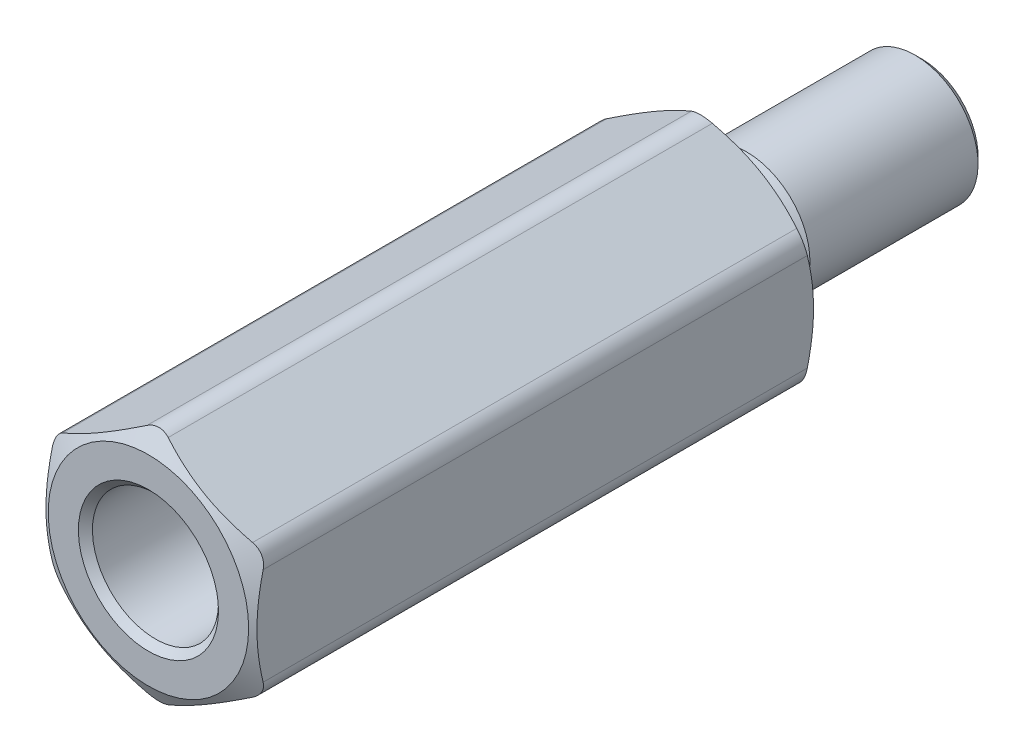
SolidWorks part; units mm, degrees
material "6061-T6 (SS)"
ref_plane "Front Plane" through (0, 0, 0) normal (0, 0, 1) x (1, 0, 0)
ref_plane "Top Plane" through (0, 0, 0) normal (0, 1, 0) x (1, 0, 0)
ref_plane "Right Plane" through (0, 0, 0) normal (1, 0, 0) x (0, 0, -1)
sketch "Sketch1" plane through (0, 0, 0) normal (0, 0, 1) x (1, 0, 0)
  line L1 (2.3813, 1.3748) -> (0, 2.7496)
  line L2 (0, 2.7496) -> (-2.3813, 1.3748)
  line L3 (-2.3813, 1.3748) -> (-2.3813, -1.3748)
  line L4 (-2.3813, -1.3748) -> (0, -2.7496)
  line L5 (0, -2.7496) -> (2.3813, -1.3748)
  line L6 (2.3813, -1.3748) -> (2.3813, 1.3748)
  circle A0 centre (0, 0) radius 2.3813 construction
  point P10 (0, -2.3813)
  dimension "Hex Size" = 4.7625
sketch "Sketch2" plane through (0, 0, 0) normal (1, 0, 0) x (0, 0, -1)
  line L0 (4.7625, 0) -> (-12.7, 0) construction
  line L2 (0, 1.4224) -> (0, -1.4224) construction
  line L3 (-6.35, 1.4224) -> (-6.35, -1.4224) construction
  line L4 (-13.4441, 1.5083) -> (-13.0473, 0.8209) construction
  line L5 (-13.0473, 0.8209) -> (-12.6504, 1.5083) construction
  line L6 (-12.6504, 1.5083) -> (-13.4441, 1.5083) construction
  line L7 (-13.3945, 1.4224) -> (-12.7, 1.4224) construction
  line L8 (-13.0969, 0.9068) -> (-12.9977, 0.9068) construction
  line L9 (-13.0473, 0.9068) -> (-13.0473, 0.8209) construction
  line L10 (-13.0473, 1.4224) -> (-13.0473, 1.5083) construction
  line L11 (4.7228, 1.4911) -> (5.3578, 1.4911) construction
  line L12 (5.3578, 1.4911) -> (5.0403, 0.9412) construction
  line L13 (5.0403, 0.9412) -> (4.7228, 1.4911) construction
  line L14 (4.7625, 1.4224) -> (5.3181, 1.4224) construction
  line L15 (5.0006, 1.01) -> (5.08, 1.01) construction
  line L16 (5.0403, 1.01) -> (5.0403, 0.9412) construction
  line L17 (5.0403, 1.4224) -> (5.0403, 1.4911) construction
  line L18 (0, 2.7496) -> (-12.7, 2.7496) construction
  point P6 (0, 0)
  point P9 (-6.35, 0)
  dimension "Length" = 12.7
sketch "Sketch3" plane through (0, 0, 0) normal (1, 0, 0) x (0, 0, -1)
  line L0 (-6.35, 0) -> (4.7625, 0)
  line L1 (-6.35, 1.4224) -> (-6.35, -1.4224) construction
  line L2 (4.7625, 0) -> (4.7625, 1.2636)
  line L3 (4.7625, 1.2636) -> (4.6038, 1.4224)
  line L4 (4.6038, 1.4224) -> (0.8096, 1.4224)
  line L5 (0.8096, 1.4224) -> (0.5715, 1.01)
  line L6 (-6.35, 0) -> (-6.35, 1.2637)
  line L7 (-6.35, 1.2637) -> (-6.5088, 1.4224)
  line L8 (-6.5088, 1.4224) -> (-12.5412, 1.4224)
  line L9 (-12.5412, 1.4224) -> (-12.7, 1.5811)
  line L10 (4.6038, 0) -> (4.6038, -1.4224) construction
  line L11 (-12.7, 1.5811) -> (-12.7, 2.3812)
  line L12 (-12.7, 2.3812) -> (0, 2.3812)
  line L14 (0.5715, 1.01) -> (0.1587, 1.01)
  line L15 (0, 1.1687) -> (0, 2.3812)
  arc A0 (0, 1.1687) -> (0.1587, 1.01) centre (0.1587, 1.1687) ccw
  point P5 (-12.7, -2.3813)
  point P8 (-10.7156, -1.4224)
  point P9 (3.175, -1.4224)
  point P27 (0, 1.01)
  dimension "D4" = 0.1588
  dimension "D2" = 0.1588
  dimension "D1" = 45
  dimension "D6" = 1.5875
  dimension "D7" = 60
  dimension "D3" = 1.9844
  dimension "D5" = 0.5715
revolve "Revolve1" add sketch "Sketch3" angle 360 about L0 region at (0, 1.2292, 3.2483)
sketch "Sketch4" plane through (0, 0, 12.7) normal (0, 0, 1) x (1, 0, 0)
  line L0 (0, 2.3812) -> (0, 1.4224) construction
  line L1 (-2.3813, 1.3748) -> (-2.3813, -1.3748)
  line L2 (-2.3813, -1.3748) -> (0, -2.7496)
  line L3 (0, -2.7496) -> (2.3813, -1.3748)
  line L4 (2.3813, -1.3748) -> (2.3812, 1.3748)
  line L5 (2.3812, 1.3748) -> (0, 2.7496)
  line L6 (0, 2.7496) -> (-2.3813, 1.3748)
  circle A0 centre (0, 0) radius 2.3813 construction
  circle A1 centre (0, 0) radius 1.9018
  circle A2 centre (0, 0) radius 2.3813 construction
  point P16 (0, 1.9018)
extrude "Boss-Extrude1" add sketch "Sketch4" against normal up to surface (12.7 mm away) up to face at (0, 2.3812, 0)
sketch "Sketch5" plane through (0, 0, 12.7) normal (0, 0, 1) x (1, 0, 0)
  line L0 (-0.8159, 1.1652) -> (0.8159, -1.1652) construction
  line L1 (0, 1.4224) -> (0, -1.4224) construction
  line L3 (0, -2.9435) -> (0, 2.9435) construction
  circle A0 centre (0, 0) radius 2.2622
  point P11 (0.8159, -1.1652)
  dimension "D1" = 4.5244
  dimension "D2" = 35
extrude "Cut-Extrude1" cut sketch "Sketch5" against normal through all draft 60 flip side to cut
sketch "Sketch6" plane through (0, 0, 0) normal (0, 0, -1) x (-1, 0, 0)
  circle A0 centre (0, 0) radius 2.2622
  circle A1 centre (0, 0) radius 2.2622 construction
extrude "Cut-Extrude2" cut sketch "Sketch6" against normal through all draft 60 flip side to cut
fillet "Fillet1" radius 0.4763 6 edges at (0, 2.7496, 6.35) (-2.3813, -1.3748, 6.35) (0, -2.7496, 6.35) (2.3813, -1.3748, 6.35) (2.3812, 1.3748, 6.35) (-2.3813, 1.3748, 6.35)
sketch "Drawing1" plane through (0, 0, 0) normal (1, 0, 0) x (0, 0, -1)
  line L0 (-12.7, 1.4224) -> (-6.35, 1.4224) construction
  line L1 (-6.35, 1.4224) -> (-6.35, -1.4224) construction
  line L2 (-6.35, -1.4224) -> (-12.7, -1.4224) construction
sketch "Sketch7" [suppressed] plane through (0, 0, 0) normal (-1, 0, 0) x (0, 0, 1)
  line L0 (-5.0006, 1.01) -> (-5.08, 1.01)
  line L1 (-5.08, 1.01) -> (-5.338, 1.4568)
  line L2 (-5.3578, 1.4911) -> (-5.0403, 0.9412) construction
  line L3 (-5.338, 1.4568) -> (-4.7427, 1.4568)
  line L4 (-5.0403, 0.9412) -> (-4.7228, 1.4911) construction
  line L5 (-4.7427, 1.4568) -> (-5.0006, 1.01)
  line L6 (-5.0403, 1.4224) -> (-5.0403, 1.4911) construction
  point P12 (-5.0403, 1.4568)
sketch "Sketch8" [suppressed] plane through (0, 0, -4.7625) normal (0, 0, -1) x (-1, 0, 0)
  circle A0 centre (0, 0) radius 1.4224
curve "Helix/Spiral1" [suppressed] pitch 0.635 height 4.6196 turns 7.275
sweep "Cut-Sweep1" [suppressed] cut profiles "Sketch7" path "Helix/Spiral1"
sketch "Sketch9" [suppressed] plane through (0, 0, 6.35) normal (0, 0, 1) x (1, 0, 0)
  circle A0 centre (0, 0) radius 1.5811
extrude "Boss-Extrude2" [suppressed] add sketch "Sketch9" along normal up to surface (6.35 mm away)
sketch "Sketch10" [suppressed] plane through (0, 0, 0) normal (1, 0, 0) x (0, 0, -1)
  line L0 (4.7625, 0) -> (-12.7, 0) construction
  line L1 (-6.35, 1.4224) -> (-12.7, 1.4224)
  line L2 (-6.35, 1.4224) -> (-6.35, 0)
  line L3 (-6.35, 0) -> (-12.7, 0)
  line L4 (-12.7, 1.4224) -> (-12.7, 0)
revolve "Revolve2" [suppressed] add sketch "Sketch10" angle 360 about L0
sketch "Sketch11" [suppressed] plane through (0, 0, 12.7) normal (0, 0, 1) x (1, 0, 0)
  circle A0 centre (0, 0) radius 1.4224
  circle A1 centre (0, 0) radius 1.4224 construction
sketch "Sketch12" [suppressed] plane through (0, 0, 0) normal (1, 0, 0) x (0, 0, -1)
  line L0 (-13.0969, 0.9068) -> (-12.9977, 0.9068)
  line L1 (-12.9977, 0.9068) -> (-12.6752, 1.4654)
  line L2 (-13.0473, 0.8209) -> (-12.6504, 1.5083) construction
  line L3 (-12.6752, 1.4654) -> (-13.4193, 1.4654)
  line L4 (-13.4441, 1.5083) -> (-13.0473, 0.8209) construction
  line L5 (-13.4193, 1.4654) -> (-13.0969, 0.9068)
  line L6 (-13.0473, 1.4224) -> (-13.0473, 1.5083) construction
  point P12 (-13.0473, 1.4654)
curve "Helix/Spiral2" [suppressed] pitch 0.7937 height 7.1437 turns 9
sweep "Cut-Sweep2" [suppressed] cut profiles "Sketch12" path "Helix/Spiral2"
combine bodies "Combine1" [suppressed] operation type subtract main body 113 bodies to subtract 114
sketch "Sketch13" [suppressed] plane through (0, 0, 12.7) normal (0, 0, 1) x (1, 0, 0)
  circle A0 centre (0, 0) radius 1.4732
  dimension "D1" = 0.0508
extrude "Cut-Extrude3" [suppressed] cut sketch "Sketch13" against normal through all draft 45
equation "\"Thread Pitch (B)/8@Sketch2\"=\"Thread Pitch (B)@Sketch2\"/8"
equation "\"Thread Pitch (A)/8@Sketch2\"=\"Thread Pitch (A)@Sketch2\"/8"
equation "\"D1@Sketch5\" = \"Hex Size@Sketch1\" * .95"
equation "\"D1@Fillet1\" = \"Hex Size@Sketch1\" * .1"
equation "\"D2@Sketch3\" = \"Thread Pitch (A)@Sketch2\" * .25"
equation "\"D4@Sketch3\" = \"D2@Sketch3\""
equation "\"D6@Sketch3\" = \"Thread Pitch (A)@Sketch2\" * 2.5"
equation "\"D3@Helix/Spiral1\" = \"Thread Length (A)@Sketch2\" - \"D5@Sketch3\" * .25"
equation "\"D4@Helix/Spiral1\" = \"Thread Pitch (A)@Sketch2\""
equation "\"D3@Sketch3\" = \"Thread Pitch (B)@Sketch2\" * 2.5"
equation "\"D5@Sketch3\" = \"Thread Length (A)@Sketch2\" * .12"
equation "\"D3@Helix/Spiral2\" = \"Minimum Thread Length (B)@Sketch2\" + \"Thread Pitch (B)@Sketch2\""
equation "\"D4@Helix/Spiral2\" = \"Thread Pitch (B)@Sketch2\""
